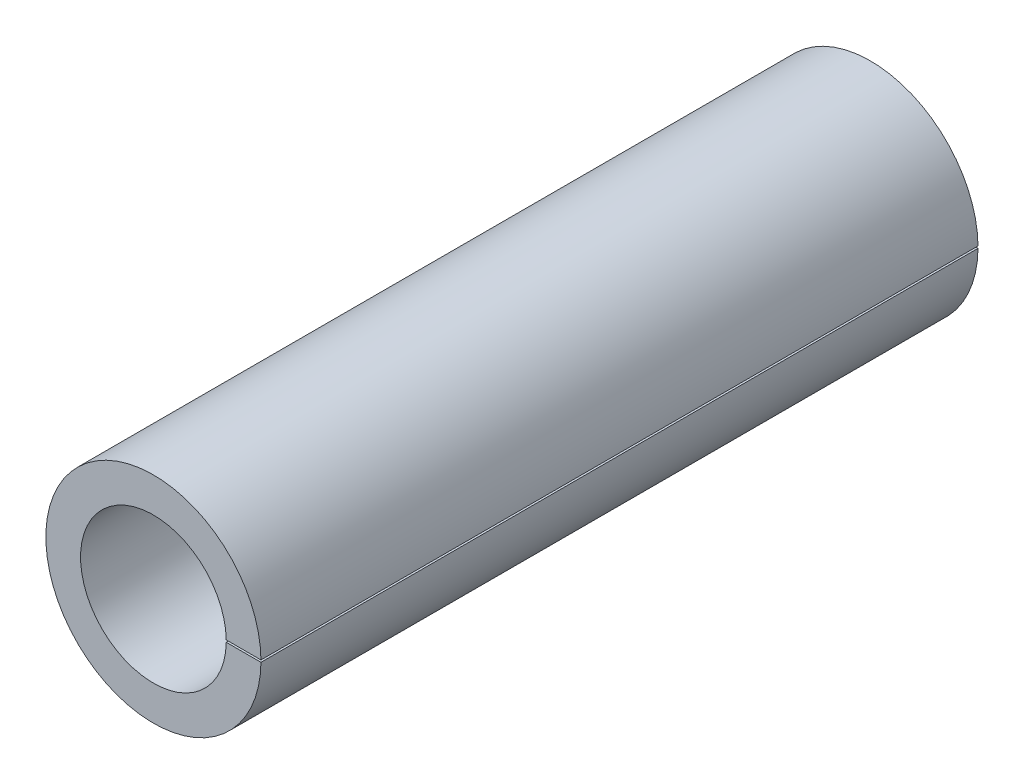
SolidWorks part; units mm, degrees
ref_plane "Front Plane" through (0, 0, 0) normal (0, 0, 1) x (1, 0, 0)
ref_plane "Top Plane" through (0, 0, 0) normal (0, 1, 0) x (1, 0, 0)
ref_plane "Right Plane" through (0, 0, 0) normal (1, 0, 0) x (0, 0, -1)
sketch "Sketch1" plane through (0, 0, 0) normal (0, 0, 1) x (1, 0, 0)
  line L0 (-4.7625, 0) -> (4.7625, 0) construction
  line L1 (0, 0) -> (2.281, -2.281) construction
  line L2 (3.2258, 0) -> (-3.2258, 0) construction
  circle A0 centre (0, 0) radius 4.7625 construction
  circle A1 centre (0, 0) radius 3.2258 construction
  point P4 (0, 4.7625)
  point P7 (0, 0)
  point P8 (0, 3.2258)
  point P9 (0, -3.2258)
  point P12 (2.281, -2.281)
  point P14 (0, 0)
  dimension "D1" = 45
  dimension "OD" = 9.525
  dimension "ID" = 6.4516
sketch "Sketch2" plane through (0, 0, 0) normal (1, 0, 0) x (0, 0, -1)
  line L0 (-15.875, 4.7625) -> (15.875, 4.7625) construction
  line L1 (-15.875, 3.2258) -> (15.875, 3.2258) construction
  line L3 (15.875, -3.2258) -> (-15.875, -3.2258) construction
  point P2 (0, 4.7625)
  point P6 (0, 3.2258)
  point P9 (0, -3.2258)
  dimension "Length" = 31.75
sketch "Sketch3" plane through (0, 0, 0) normal (0, 0, 1) x (1, 0, 0)
  line L0 (0, -0.045) -> (0, 0.045) construction
  line L1 (0, 0.045) -> (4.7623, 0.045) construction
  line L2 (0, -0.045) -> (4.7623, -0.045) construction
  line L3 (3.2255, 0.045) -> (4.7623, 0.045)
  line L4 (3.2255, -0.045) -> (4.7623, -0.045)
  circle A1 centre (0, 0) radius 4.7625 construction
  circle A4 centre (0, 0) radius 3.2258 construction
  arc A5 (4.7623, 0.045) -> (4.7623, -0.045) centre (0, 0) ccw
  arc A6 (3.2255, 0.045) -> (3.2255, -0.045) centre (0, 0) ccw
  point P7 (0, 0)
  dimension "D1" = 0.09
extrude "Boss-Extrude1" add sketch "Sketch3" along normal up to vertex (15.875 mm away) and the other way up to vertex (15.875 mm away) up to point (0, 4.7625, 15.875) other way up to point (0, 4.7625, -15.875)
